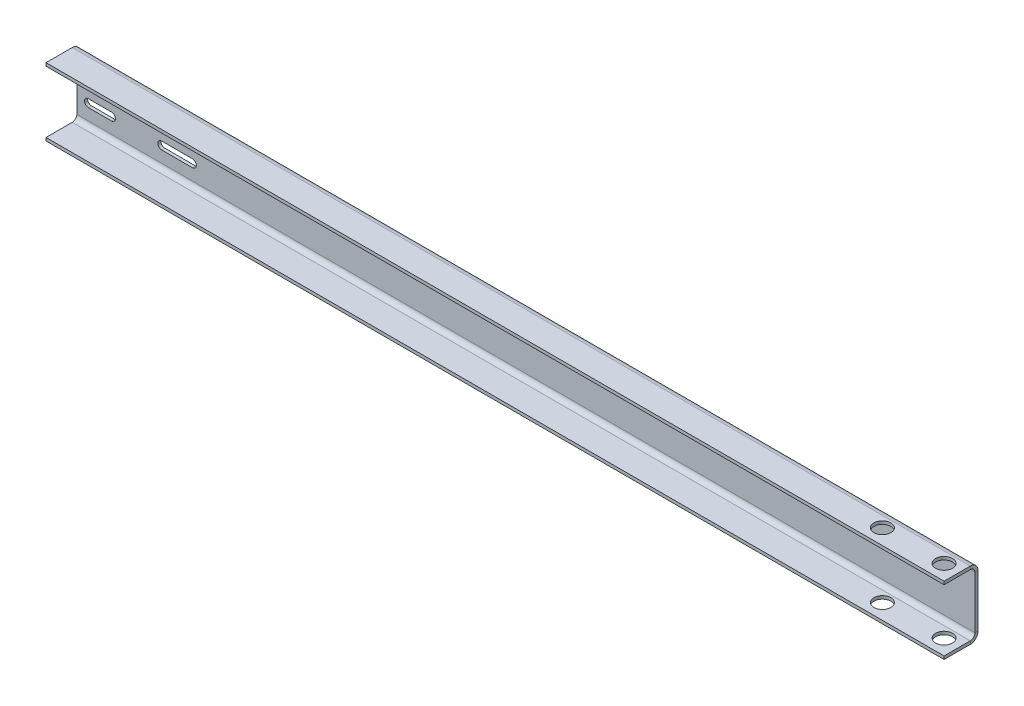
SolidWorks part; units mm, degrees
note: The reader was unsure of these and kept them because the rebuilt part matched: flange length of "Edge-Flange1", "Edge-Flange2".
material "ASTM A36 Steel"
ref_plane "Front Plane" through (0, 0, 0) normal (0, 0, 1) x (1, 0, 0)
ref_plane "Top Plane" through (0, 0, 0) normal (0, 1, 0) x (1, 0, 0)
ref_plane "Right Plane" through (0, 0, 0) normal (1, 0, 0) x (0, 0, -1)
sketch "Sketch1" plane through (0, 0, 0) normal (0, 0, 1) x (1, 0, 0)
  line L1 (299.481, 88) -> (-865.519, 88)
  line L2 (299.481, 88) -> (299.481, 0)
  line L3 (299.481, 0) -> (-865.519, 0)
  line L4 (-865.519, 88) -> (-865.519, 0)
  dimension "D1" = 88
  dimension "D2" = 1165
base flange "Base-Flange1" sketch "Sketch1" thickness 4 reverse thickness direction no parameters "D1"=2.5
edge flange "Edge-Flange1" sketch "Sketch8" flange angle 90 flange length 44 flange position material inside bend radius 6 thickness 4 relief rectangular parameters "D6"=10
sketch "Sketch8" plane through (0, 88, 0) normal (0, -1, 0) x (1, 0, 0)
  line L1 (299.481, 0) -> (-865.519, 0) construction
  line L2 (-865.519, 0) -> (-865.519, 40)
  line L3 (-865.519, 40) -> (299.481, 40)
  line L4 (299.481, 40) -> (299.481, 0)
  line L5 (299.481, 0) -> (-865.519, 0)
bend "EdgeBend1" bend radius 6 bend angle 90 parameters "D5"=1
edge flange "Edge-Flange2" sketch "Sketch11" flange angle 90 flange length 44 flange position material inside bend radius 6 thickness 4 relief rectangular parameters "D6"=10
sketch "Sketch11" plane through (0, 0, 0) normal (0, 1, 0) x (-1, 0, 0)
  line L1 (865.519, 0) -> (-299.481, 0) construction
  line L2 (-299.481, 0) -> (-299.481, 40)
  line L3 (-299.481, 40) -> (865.519, 40)
  line L4 (865.519, 40) -> (865.519, 0)
  line L5 (865.519, 0) -> (-299.481, 0)
bend "EdgeBend2" bend radius 6 bend angle 90 parameters "D5"=2
sketch "Sketch12" plane through (0, 0, 0) normal (0, -1, 0) x (1, 0, 0)
  line L0 (299.481, 40) -> (299.481, 6) construction
  circle A0 centre (279.481, 20) radius 11
  circle A1 centre (199.481, 20) radius 11
  dimension "D3" = 22
  dimension "D4" = 22
  dimension "D1" = 20
  dimension "D2" = 80
extrude "Cut-Extrude1" cut sketch "Sketch12" against normal through all both and the other way through all normal cut yes
sketch "Sketch13" plane through (0, 0, -4) normal (0, 0, -1) x (-1, 0, 0)
  line L0 (865.519, 0) -> (-299.481, 0) construction
  line L3 (850.519, 30) -> (820.519, 30) construction
  line L4 (850.519, 25) -> (820.519, 25)
  line L5 (850.519, 35) -> (820.519, 35)
  line L6 (865.519, 78) -> (865.519, 10) construction
  line L7 (755.519, 30) -> (715.519, 30) construction
  line L8 (755.519, 25) -> (715.519, 25)
  line L9 (755.519, 35) -> (715.519, 35)
  arc A0 (755.519, 25) -> (755.519, 35) centre (755.519, 30) ccw
  arc A1 (715.519, 35) -> (715.519, 25) centre (715.519, 30) ccw
  arc A2 (850.519, 25) -> (850.519, 35) centre (850.519, 30) ccw
  arc A3 (820.519, 35) -> (820.519, 25) centre (820.519, 30) ccw
  point P6 (735.519, 30)
  point P10 (835.519, 30)
  point P18 (750.519, 30)
  point P19 (720.519, 30)
  dimension "D5" = 30
  dimension "D6" = 30
  dimension "D4" = 30
  dimension "D1" = 15
  dimension "D2" = 100
  dimension "D3" = 10
  dimension "D7" = 10
extrude "Cut-Extrude2" cut sketch "Sketch13" against normal through all normal cut yes
sketch "Bend-Lines1" [suppressed] plane through (0, 0, 0) normal (0, 1, 0) x (1, 0, 0)
sketch "Bounding-Box1" [suppressed] plane through (0, 0, 0) normal (0, 1, 0) x (1, 0, 0)
sheet metal parameters "Sheet-Metal1" thickness 4 parameters "D1"=2.5
flat pattern "Flat-Pattern1" [suppressed]
sketch "Bend-Lines2" plane through (0, 0, 0) normal (0, 1, 0) x (1, 0, 0)
sketch3d "Bounding-Box2" [suppressed]
  line L0 (865.519, 0, 0) -> (-299.481, 0, 0) construction
  line L1 (865.519, 88, 0) -> (-299.481, 88, 0) construction
  line L2 (865.519, 0, 0) -> (865.519, 88, 0) construction
  line L3 (-299.481, 0, 0) -> (-299.481, 88, 0) construction
sheet metal parameters "Sheet-Metal2" thickness 4 parameters "D1"=2.5
flat pattern "Flat-Pattern1"
sketch "Bend-Lines2" plane through (0, 0, 0) normal (0, 0, 1) x (1, 0, 0)
  line L0 (299.481, 84.2832) -> (-865.519, 84.2832) construction
  line L1 (299.481, 84.2832) -> (-865.519, 84.2832) construction
sketch3d "Bounding-Box2" [suppressed]
  line L0 (-865.519, 0, 0) -> (299.481, 0, 0) construction
  line L1 (-865.519, 124.5664, 0) -> (299.481, 124.5664, 0) construction
  line L2 (-865.519, 0, 0) -> (-865.519, 124.5664, 0) construction
  line L3 (299.481, 0, 0) -> (299.481, 124.5664, 0) construction
bend of the flat pattern "Flatten-<EdgeBend1>1"
sheet metal parameters "Sheet-Metal3" thickness 4 parameters "D1"=2.5
flat pattern "Flat-Pattern1"
sketch "Bend-Lines2" plane through (0, 0, 0) normal (0, 0, 1) x (1, 0, 0)
  line L0 (299.481, 84.2832) -> (-865.519, 84.2832) construction
  line L1 (299.481, 84.2832) -> (-865.519, 84.2832) construction
  line L2 (-865.519, 3.7168) -> (299.481, 3.7168) construction
  line L3 (-865.519, 3.7168) -> (299.481, 3.7168) construction
sketch3d "Bounding-Box2" [suppressed]
  line L0 (-865.519, -36.5664, 0) -> (299.481, -36.5664, 0) construction
  line L1 (-865.519, 124.5664, 0) -> (299.481, 124.5664, 0) construction
  line L2 (-865.519, -36.5664, 0) -> (-865.519, 124.5664, 0) construction
  line L3 (299.481, -36.5664, 0) -> (299.481, 124.5664, 0) construction
bend of the flat pattern "Flatten-<EdgeBend1>1"
bend of the flat pattern "Flatten-<EdgeBend2>1"
sheet metal parameters "Sheet-Metal4" thickness 4 parameters "D1"=2.5
flat pattern "Flat-Pattern1"
sketch "Bend-Lines2" plane through (0, 0, 0) normal (0, 0, 1) x (1, 0, 0)
  line L0 (299.481, 84.2832) -> (-865.519, 84.2832) construction
  line L1 (299.481, 84.2832) -> (-865.519, 84.2832) construction
  line L2 (-865.519, 3.7168) -> (299.481, 3.7168) construction
  line L3 (-865.519, 3.7168) -> (299.481, 3.7168) construction
sketch3d "Bounding-Box2" [suppressed]
  line L0 (-865.519, -36.5664, 0) -> (299.481, -36.5664, 0) construction
  line L1 (-865.519, 124.5664, 0) -> (299.481, 124.5664, 0) construction
  line L2 (-865.519, -36.5664, 0) -> (-865.519, 124.5664, 0) construction
  line L3 (299.481, -36.5664, 0) -> (299.481, 124.5664, 0) construction
bend of the flat pattern "Flatten-<EdgeBend1>1"
bend of the flat pattern "Flatten-<EdgeBend2>1"
sheet metal parameters "Sheet-Metal5" thickness 4 parameters "D1"=2.5
flat pattern "Flat-Pattern1"
sketch "Bend-Lines2" plane through (0, 0, 0) normal (0, 0, 1) x (1, 0, 0)
  line L0 (299.481, 84.2832) -> (-865.519, 84.2832) construction
  line L1 (299.481, 84.2832) -> (-865.519, 84.2832) construction
  line L2 (-865.519, 3.7168) -> (299.481, 3.7168) construction
  line L3 (-865.519, 3.7168) -> (299.481, 3.7168) construction
sketch3d "Bounding-Box2" [suppressed]
  line L0 (-865.519, -36.5664, 0) -> (299.481, -36.5664, 0) construction
  line L1 (-865.519, 124.5664, 0) -> (299.481, 124.5664, 0) construction
  line L2 (-865.519, -36.5664, 0) -> (-865.519, 124.5664, 0) construction
  line L3 (299.481, -36.5664, 0) -> (299.481, 124.5664, 0) construction
bend of the flat pattern "Flatten-<EdgeBend1>1"
bend of the flat pattern "Flatten-<EdgeBend2>1"
